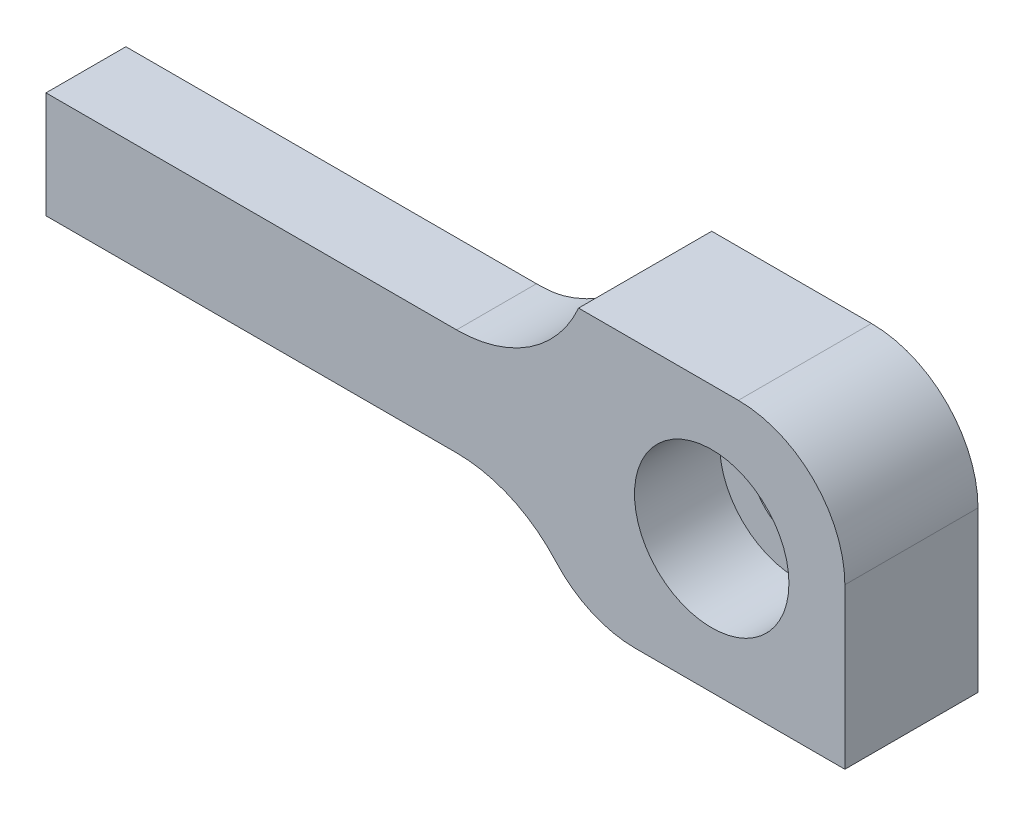
SolidWorks part; units mm, degrees
ref_plane "Front Plane" through (0, 0, 0) normal (0, 0, 1) x (1, 0, 0)
ref_plane "Top Plane" through (0, 0, 0) normal (0, 1, 0) x (1, 0, 0)
ref_plane "Right Plane" through (0, 0, 0) normal (1, 0, 0) x (0, 0, -1)
sketch "Sketch1" plane through (0, 0, 0) normal (0, 0, 1) x (1, 0, 0)
  line L1 (-31.75, -6.35) -> (6.35, -6.35)
  line L2 (-31.75, -6.35) -> (-31.75, 6.35)
  line L3 (-31.75, 6.35) -> (6.35, 6.35)
  line L4 (6.35, -6.35) -> (6.35, 6.35)
  line L5 (-31.75, -6.35) -> (6.35, 6.35) construction
  line L6 (-31.75, 6.35) -> (6.35, -6.35) construction
  point P0 (0, 0)
  point P6 (0, 0)
  point P7 (0, 0)
  dimension "D1" = 38.1
  dimension "D2" = 12.7
  dimension "D3" = 6.35
  dimension "D4" = 6.35
extrude "Boss-Extrude1" add sketch "Sketch1" along normal blind 6.35
sketch "Sketch2" plane through (0, 0, 6.35) normal (0, 0, 1) x (1, 0, 0)
  circle A0 centre (0, 0) radius 2.159
  dimension "D1" = 4.318
extrude "Cut-Extrude1" cut sketch "Sketch2" against normal through all
sketch "Sketch3" plane through (0, 0, 6.35) normal (0, 0, 1) x (1, 0, 0)
  circle A0 centre (0, 0) radius 3.683
  dimension "D1" = 7.366
extrude "Cut-Extrude2" cut sketch "Sketch3" against normal blind 4.064
sketch "Sketch5" plane through (0, 0, 6.35) normal (0, 0, 1) x (1, 0, 0)
  line L1 (-31.75, 6.35) -> (-6.35, 6.35)
  line L2 (-31.75, 6.35) -> (-31.75, 2.54)
  line L3 (-31.75, 2.54) -> (-6.35, 2.54)
  line L4 (-6.35, 6.35) -> (-6.35, 2.54)
  line L5 (-31.75, -6.35) -> (-6.35, -6.35)
  line L6 (-31.75, -6.35) -> (-31.75, -2.54)
  line L7 (-31.75, -2.54) -> (-6.35, -2.54)
  line L8 (-6.35, -6.35) -> (-6.35, -2.54)
  dimension "D1" = 3.81
  dimension "D2" = 25.4
extrude "Cut-Extrude3" cut sketch "Sketch5" against normal through all
sketch "Sketch6" plane through (0, 2.54, 0) normal (0, 1, 0) x (1, 0, 0)
  line L0 (-6.35, 0) -> (-6.35, -6.35) construction
  line L1 (-31.75, 0) -> (-6.35, 0)
  line L2 (-31.75, 0) -> (-31.75, -2.54)
  line L3 (-31.75, -2.54) -> (-6.35, -2.54)
  line L4 (-6.35, 0) -> (-6.35, -2.54)
  dimension "D1" = 2.54
extrude "Cut-Extrude4" cut sketch "Sketch6" against normal through all
fillet "Fillet3" radius 6.35 3 edges at (-6.35, -2.54, 4.445) (-6.35, 0, 2.54) (-6.35, 2.54, 4.445)
fillet "Fillet4" radius 5.08 2 edges at (-6.35, -6.35, 3.175) (6.35, 6.35, 3.175)
